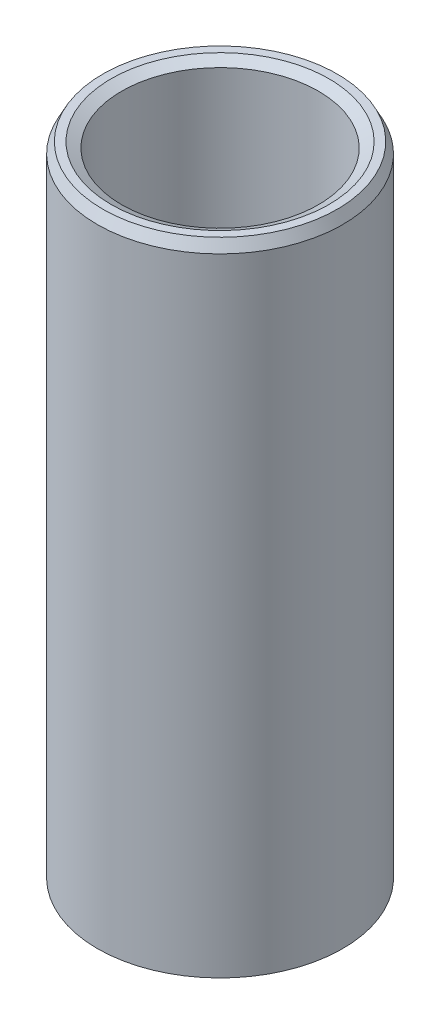
SolidWorks part; units mm, degrees
ref_plane "Front Plane" through (0, 0, 0) normal (0, 0, 1) x (1, 0, 0)
ref_plane "Top Plane" through (0, 0, 0) normal (0, 1, 0) x (1, 0, 0)
ref_plane "Right Plane" through (0, 0, 0) normal (1, 0, 0) x (0, 0, -1)
sketch "Sketch1" plane through (0, 0, 0) normal (0, 1, 0) x (1, 0, 0)
  circle A0 centre (0, 0) radius 32.5
  dimension "SLEEVE_OD" = 65
extrude "Boss-Extrude1" add sketch "Sketch1" along normal blind 170.3961
sketch "Sketch2" plane through (0, 0, 0) normal (0, 1, 0) x (1, 0, 0)
  circle A0 centre (0, 0) radius 26.0771
  dimension "BORE_D" = 52.1541
extrude "Cut-Extrude1" cut sketch "Sketch2" along normal through all
chamfer "Chamfer1" distance 2.795 angle 27.418 4 edges at (0, 170.3961, 26.0771) (0, 0, 26.0771) (0, 0, 32.5) (0, 170.3961, 32.5) first distance on face at (0, 170.3961, 26.0771) first distance on face at (0, 0, 26.0771) first distance on face at (0, 170.3961, 32.5)
